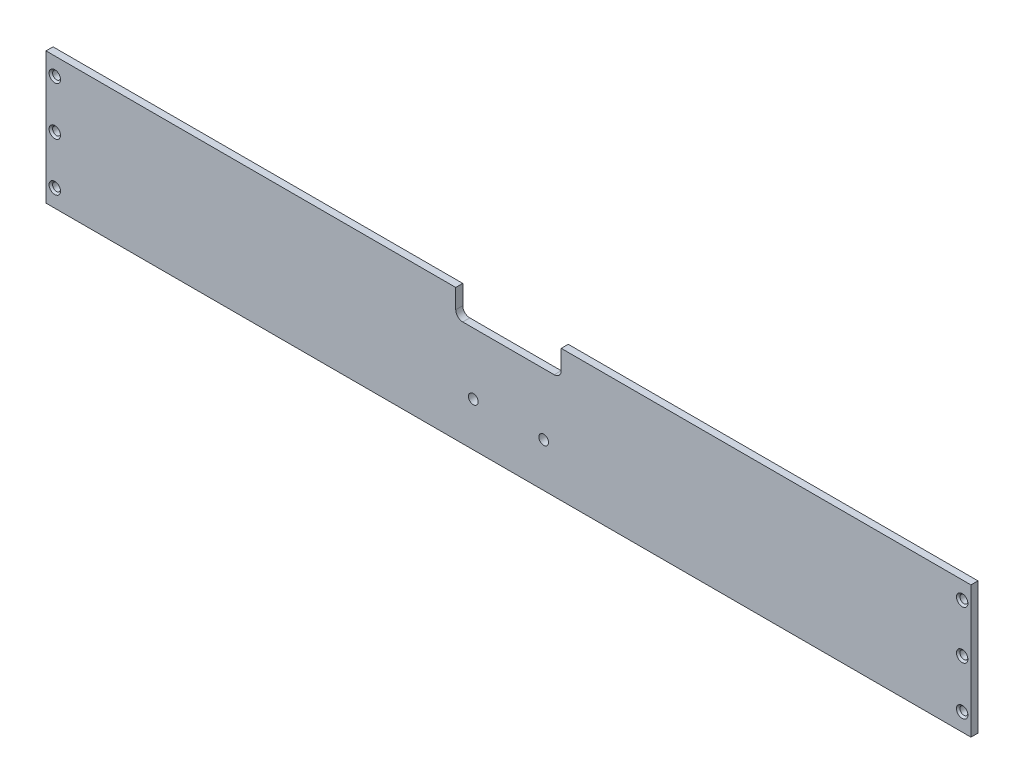
SolidWorks part; units mm, degrees
ref_plane "Piano frontale" through (0, 0, 0) normal (0, 0, 1) x (1, 0, 0)
ref_plane "Piano superiore" through (0, 0, 0) normal (0, 1, 0) x (1, 0, 0)
ref_plane "Piano destro" through (0, 0, 0) normal (1, 0, 0) x (0, 0, -1)
sketch "Schizzo1" plane through (0, 0, 0) normal (0, 0, 1) x (1, 0, 0)
  line L1 (0, 0) -> (526, 0)
  line L2 (0, 0) -> (0, 75)
  line L3 (0, 75) -> (526, 75)
  line L4 (526, 0) -> (526, 75)
  dimension "D1" = 75
  dimension "D2" = 526
extrude "Estrusione-Estrusione1" add sketch "Schizzo1" against normal blind 4
sketch "Schizzo2" plane through (0, 0, 0) normal (0, 0, 1) x (1, 0, 0)
  line L0 (263, 75) -> (263, -42.036) construction
  line L1 (526, 75) -> (0, 75) construction
  line L3 (233, 90) -> (293, 90)
  line L4 (233, 90) -> (233, 64)
  line L5 (237, 60) -> (289, 60)
  line L6 (293, 90) -> (293, 64)
  line L7 (233, 90) -> (293, 60) construction
  line L8 (233, 60) -> (293, 90) construction
  arc A0 (293, 64) -> (289, 60) centre (289, 64) cw
  arc A1 (237, 60) -> (233, 64) centre (237, 64) cw
  dimension "D3" = 4
  dimension "D1" = 60
  dimension "D2" = 30
extrude "Taglio-Estrusione1" cut sketch "Schizzo2" against normal blind 4
sketch "Schizzo3" plane through (0, 0, 0) normal (0, 0, 1) x (1, 0, 0)
  line L0 (263, 0) -> (263, 60) construction
  line L1 (0, 0) -> (526, 0) construction
  line L2 (237, 60) -> (289, 60) construction
  line L8 (526, 75) -> (526, 0) construction
  line L9 (521, 75) -> (521, 0) construction
  line L18 (0, 75) -> (0, 0) construction
  line L19 (0, 37.5) -> (526, 37.5) construction
  circle A0 centre (243, 25) radius 2.75
  circle A1 centre (283, 25) radius 2.75
  circle A2 centre (521, 65) radius 2.25
  circle A3 centre (521, 37.5) radius 2.25
  circle A4 centre (521, 10) radius 2.25
  circle A5 centre (5, 10) radius 2.25
  circle A6 centre (5, 37.5) radius 2.25
  circle A7 centre (5, 65) radius 2.25
  dimension "D11" = 4.5
  dimension "D7" = 27.5
  dimension "D2" = 25
  dimension "D3" = 20
  dimension "D6" = 5
extrude "Taglio-Estrusione2" cut sketch "Schizzo3" against normal through all
chamfer "Smusso1" distance 1 angle 45 6 edges at (523.25, 37.5, 0) (523.25, 65, 0) (518.75, 10, 0) (7.25, 10, 0) (2.75, 37.5, 0) (2.75, 65, 0)
